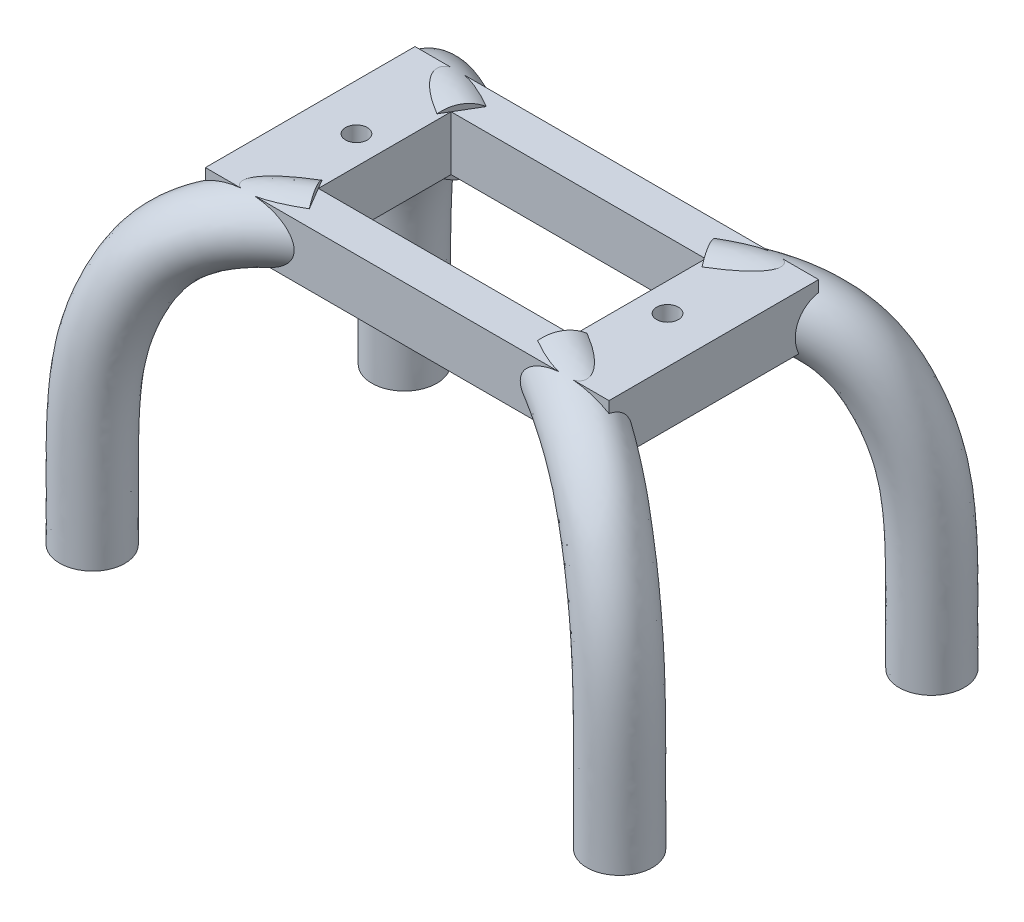
SolidWorks part; units mm, degrees
ref_plane "前视基准面" through (0, 0, 0) normal (0, 0, 1) x (1, 0, 0)
ref_plane "上视基准面" through (0, 0, 0) normal (0, 1, 0) x (1, 0, 0)
ref_plane "右视基准面" through (0, 0, 0) normal (1, 0, 0) x (0, 0, -1)
sketch "草图1" plane through (0, 0, 0) normal (0, 1, 0) x (1, 0, 0)
  line L0 (-5.6, 0) -> (-5.6, 12.535) construction
  line L1 (6.1, -6.1) -> (-17.3, -6.1)
  line L2 (6.1, -6.1) -> (6.1, 6.1)
  line L3 (6.1, 6.1) -> (-17.3, 6.1)
  line L4 (-17.3, -6.1) -> (-17.3, 6.1)
  line L5 (6.1, -6.1) -> (-17.3, 6.1) construction
  line L6 (6.1, 6.1) -> (-17.3, -6.1) construction
  line L7 (12.9533, -9.6358) -> (-24.1533, -9.6358)
  line L8 (12.9533, -9.6358) -> (12.9533, 9.6358)
  line L9 (12.9533, 9.6358) -> (-24.1533, 9.6358)
  line L10 (-24.1533, -9.6358) -> (-24.1533, 9.6358)
  line L11 (12.9533, -9.6358) -> (-24.1533, 9.6358) construction
  line L12 (12.9533, 9.6358) -> (-24.1533, -9.6358) construction
  line L13 (-19.9, 0) -> (-5.6, 0) construction
  circle A0 centre (-19.9, 0) radius 1
  circle A2 centre (8.7, 0) radius 1
  circle A3 centre (0, 0) radius 6.1 construction
  point P0 (-5.6, 0)
  point P6 (-5.6, 0)
  dimension "D4" = 2
  dimension "D1" = 23.4
  dimension "D2" = 12.2
  dimension "D3" = 14.3
extrude "凸台-拉伸1" add sketch "草图1" along normal blind 5
ref_plane "基准面3" through (-5.6, 0, 0) normal (1, 0, 0) x (0, 0, -1)
ref_axis "基准轴1" through (-5.6, 5.25, 0) along (0, -1, 0)
ref_plane "基准面2" through (-1.4524, 0, 2.4544) normal (-0.5093, 0, 0.8606) x (0, -1, 0)
sketch "草图2" plane through (-1.4524, 0, 2.4544) normal (0.5093, 0, -0.8606) x (-0.8606, 0, -0.5093)
  line L1 (25.6938, 5) -> (25.6938, 0) construction
  line L4 (4.8194, -1.05) -> (4.8194, 8.4021) construction
  line L5 (-8.3562, 5) -> (-8.3562, 0) construction
  line L6 (-8.3562, 5) -> (-8.3562, 0) construction
  line L7 (20.4583, 2.5) -> (-20.4583, 2.5) construction
  line L9 (4.8194, 5.25) -> (4.8194, -0.25) construction
  spline S0 degree 3 poles (-8.3562, 2.5) (-16.3708, 2.496) (-24.0722, -7.0947) (-23.2888, -15.0942) (-23.3586, -25.5) knots 0 0 0 0 0.354063 1 1 1 1
  point P3 (25.6938, 2.5)
  point P5 (-20.7607, -4.0959)
  dimension "D1" = 28.178
  dimension "D2" = 28
sweep "扫描1" add path "草图2" circular profile diameter 6 parameters "D3"=6
sketch "草图35" plane through (0.148, -25.6554, 0.0876) normal (0.0058, -1, 0.0034) x (1, 0.0058, 0)
  circle A0 centre (18.5026, 14.263) radius 1.475
  circle A1 centre (18.5026, 14.263) radius 3 construction
  circle A2 centre (18.5026, 14.263) radius 3 construction
  point P4 (18.3785, 14.1896)
  point P8 (18.8853, 14.4895)
  point P9 (0, 0)
  dimension "D1" = 2.95
extrude "切除-拉伸1" cut sketch "草图35" against normal blind 6
mirror "镜向1" about plane through (0, 0, 0) normal (0, 0, 1) of "切除-拉伸1", "扫描1"
mirror "镜向2" about plane through (-5.6, 0, 0) normal (1, 0, 0) of "镜向1"
sketch "草图36" plane through (0, 5, 0) normal (0, 1, 0) x (1, 0, 0)
  line L0 (-24.1533, -9.6358) -> (12.9533, -9.6358) construction
  line L1 (30, -20) -> (-30, -20)
  line L2 (30, -20) -> (30, 20)
  line L3 (30, 20) -> (-30, 20)
  line L4 (-30, -20) -> (-30, 20)
  line L5 (30, -20) -> (-30, 20) construction
  line L6 (30, 20) -> (-30, -20) construction
  line L7 (12.9533, -9.6358) -> (12.9533, 9.6358) construction
  line L8 (12.9533, 9.6358) -> (-24.1533, 9.6358) construction
  line L9 (-24.1533, 9.6358) -> (-24.1533, -9.6358) construction
  line L10 (-24.1533, -9.6358) -> (12.9533, -9.6358)
  line L11 (12.9533, -9.6358) -> (12.9533, 9.6358)
  line L12 (12.9533, 9.6358) -> (-24.1533, 9.6358)
  line L13 (-24.1533, 9.6358) -> (-24.1533, -9.6358)
  point P0 (0, 0)
  dimension "D1" = 40
  dimension "D2" = 60
extrude "凸台-拉伸2" [suppressed] add sketch "草图36" against normal blind 5
sketch "草图45" [suppressed] plane through (0, 0, 0) normal (0, -1, 0) x (1, 0, 0)
  line L0 (30, -20) -> (-30, -20) construction
  line L1 (30, 20) -> (30, -20) construction
  line L2 (-30, 20) -> (30, 20) construction
  line L3 (-30, -20) -> (-30, 20) construction
  line L4 (30, -20) -> (-30, -20)
  line L5 (30, 20) -> (30, -20)
  line L6 (-30, 20) -> (30, 20)
  line L7 (-30, -20) -> (-30, 20)
  line L9 (27, -17) -> (-27, -17)
  line L10 (27, -17) -> (27, 17)
  line L11 (27, 17) -> (-27, 17)
  line L12 (-27, -17) -> (-27, 17)
  line L13 (27, -17) -> (-27, 17) construction
  line L14 (27, 17) -> (-27, -17) construction
  point P3 (0, 0)
  dimension "D1" = 3
  dimension "D2" = 3
extrude "凸台-拉伸3" [suppressed] add sketch "草图45" along normal blind 30
